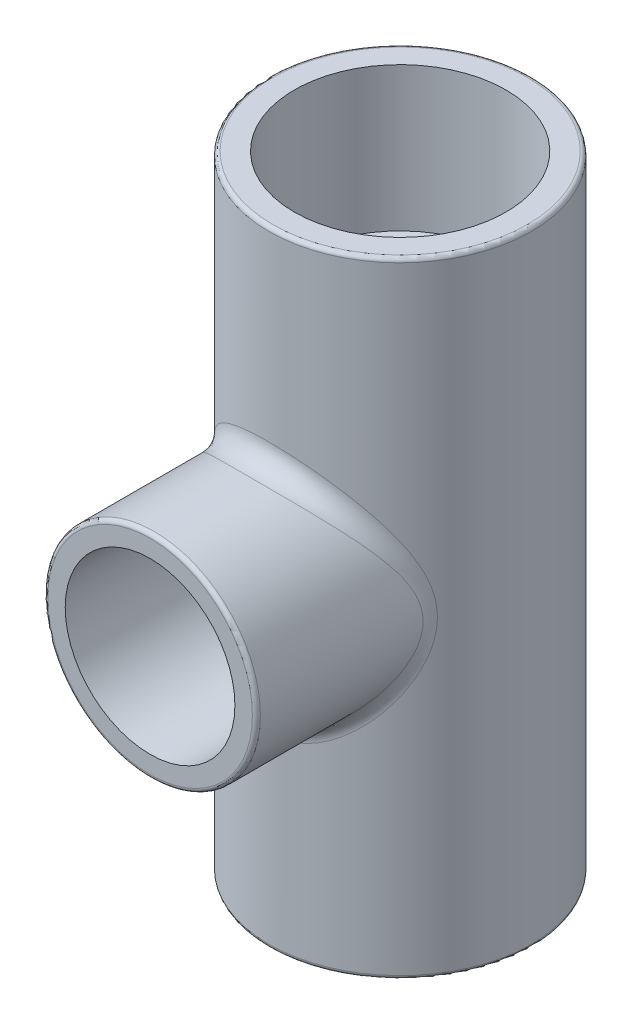
SolidWorks part; units mm, degrees
ref_plane "Front Plane" through (0, 0, 0) normal (0, 0, 1) x (1, 0, 0)
ref_plane "Top Plane" through (0, 0, 0) normal (0, 1, 0) x (1, 0, 0)
ref_plane "Right Plane" through (0, 0, 0) normal (1, 0, 0) x (0, 0, -1)
sketch "Sketch1" plane through (0, 0, 0) normal (0, 1, 0) x (1, 0, 0)
  circle A0 centre (0, 0) radius 412
  circle A1 centre (0, 0) radius 656.5
  dimension "D1" = 824
  dimension "D2" = 1313
extrude "Boss-Extrude1" add sketch "Sketch1" along normal blind 3125
sketch "Sketch2" plane through (0, 3125, 0) normal (0, 1, 0) x (1, 0, 0)
  circle A0 centre (0, 0) radius 529
  dimension "D1" = 1058
extrude "Cut-Extrude1" cut sketch "Sketch2" against normal blind 720
sketch "Sketch3" plane through (0, 0, 0) normal (0, -1, 0) x (1, 0, 0)
  circle A0 centre (0, 0) radius 529
  dimension "D1" = 1058
extrude "Cut-Extrude2" cut sketch "Sketch3" against normal blind 720
sketch "Sketch4" plane through (0, 0, 0) normal (0, 0, 1) x (1, 0, 0)
  line L0 (0, 0) -> (0, 3125) construction
  line L1 (656.5, 3125) -> (-656.5, 3125) construction
  circle A0 centre (0, 1562.5) radius 311
  circle A1 centre (0, 1562.5) radius 531.5
  dimension "D1" = 622
  dimension "D2" = 1063
extrude "Boss-Extrude2" add sketch "Sketch4" along normal blind 1250
sketch "Sketch5" plane through (0, 0, 1250) normal (0, 0, 1) x (1, 0, 0)
  line L0 (0, 1873.5) -> (0, 1251.5) construction
  circle A0 centre (0, 1562.5) radius 311 construction
  circle A1 centre (0, 1562.5) radius 311 construction
  circle A2 centre (0, 1562.5) radius 424
  dimension "D1" = 848
extrude "Cut-Extrude3" cut sketch "Sketch5" against normal blind 690
sketch "Sketch6" plane through (0, 0, 0) normal (0, -1, 0) x (1, 0, 0)
  circle A0 centre (0, 0) radius 412
  dimension "D1" = 824
extrude "Cut-Extrude4" cut sketch "Sketch6" against normal through all
sketch "Sketch7" plane through (0, 0, 1250) normal (0, 0, 1) x (1, 0, 0)
  circle A1 centre (0, 1562.5) radius 311
  dimension "D1" = 622
extrude "Cut-Extrude7" cut sketch "Sketch7" against normal blind 1230
fillet "Fillet1" radius 20 1 edges at (0, 3125, 656.5)
fillet "Fillet2" radius 20 1 edges at (0, 0, 656.5)
fillet "Fillet3" radius 20 1 edges at (531.5, 1562.5, 1250)
fillet "Fillet4" radius 100 1 edges at (524.4649, 1648.6906, 394.8782)
